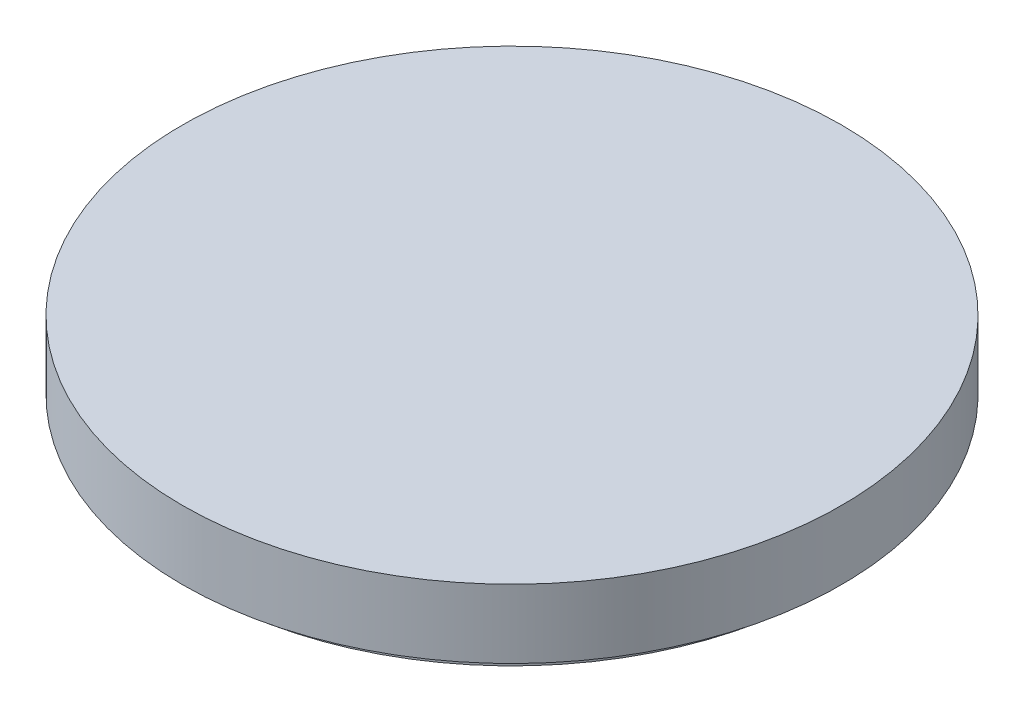
SolidWorks part; units mm, degrees
ref_plane "Front Plane" through (0, 0, 0) normal (0, 0, 1) x (1, 0, 0)
ref_plane "Top Plane" through (0, 0, 0) normal (0, 1, 0) x (1, 0, 0)
ref_plane "Right Plane" through (0, 0, 0) normal (1, 0, 0) x (0, 0, -1)
sketch "Sketch1" plane through (0, 0, 0) normal (0, 1, 0) x (1, 0, 0)
  circle A0 centre (0, 0) radius 57
  circle A1 centre (0, 0) radius 60
  dimension "D1" = 120
  dimension "D2" = 114
extrude "Extrude4" add sketch "Sketch1" along normal mid plane 15 contours A0
extrude "Extrude5" add sketch "Sketch" along normal blind 7.5 and the other way blind 5
sketch "Sketch" plane through (0, 0, 0) normal (0, 1, 0) x (1, 0, 0) same geometry as "Sketch1"
